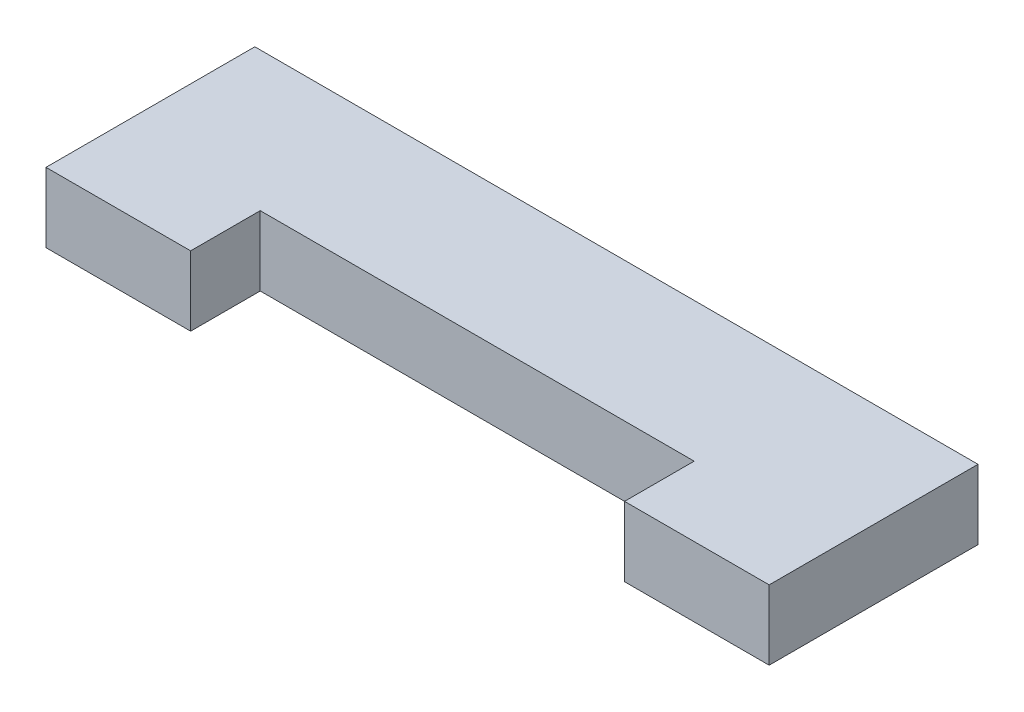
SolidWorks part; units mm, degrees
ref_plane "Front Plane" through (0, 0, 0) normal (0, 0, 1) x (1, 0, 0)
ref_plane "Top Plane" through (0, 0, 0) normal (0, 1, 0) x (1, 0, 0)
ref_plane "Right Plane" through (0, 0, 0) normal (1, 0, 0) x (0, 0, -1)
sketch "Sketch1" plane through (0, 0, 0) normal (0, 1, 0) x (1, 0, 0)
  line L0 (-20, -3.85) -> (-20, -7.7)
  line L1 (-12, -3.85) -> (12, -3.85)
  line L2 (-20, -3.85) -> (-20, 3.85)
  line L3 (-20, 3.85) -> (20, 3.85)
  line L4 (20, -3.85) -> (20, 3.85)
  line L5 (-20, -3.85) -> (20, 3.85) construction
  line L6 (-20, 3.85) -> (20, -3.85) construction
  line L7 (-20, -7.7) -> (-12, -7.7)
  line L8 (-12, -7.7) -> (-12, -3.85)
  line L9 (0, -2.2) -> (0, 2.2) construction
  line L10 (12, -7.7) -> (12, -3.85)
  line L11 (20, -7.7) -> (12, -7.7)
  line L12 (20, -3.85) -> (20, -7.7)
  line L13 (12, -3.85) -> (20, -3.85) construction
  line L14 (-20, -3.85) -> (-12, -3.85) construction
  point P0 (0, 0)
  dimension "D1" = 7.7
  dimension "D2" = 40
  dimension "D3" = 3.85
  dimension "D4" = 8
extrude "Boss-Extrude1" add sketch "Sketch1" along normal blind 3.85
equation "\"m3_hole\"= 3.5"
equation "\"m3_washer\"= 7.3"
equation "\"m3_nut\"= 5.3"
equation "\"plywood_thickness\" = 3.85"
equation "\"guide_width\"= 10.0"
equation "\"guide_length\"= 65.0"
equation "\"guide_tab_length\" = 10.0"
equation "\"guide_tab_width\" = 9.0"
equation "\"guide_thickness\" = 12.0"
equation "\"grinder_od\"= 52.0"
equation "\"grinder_id\"= 45.5"
equation "\"grinder_adjust_od\" = 58.0"
equation "\"funnel_width_from_adjust_ring\" = 13.0"
equation "\"drill_contact_diameter_small\" = 24.0"
equation "\"drill_contact_diameter_medium\" = 28.0"
equation "\"drill_contact_diameter_large\" = 39.0"
equation "\"drill_contact_diameter_tab\" = 31.0"
equation "\"drill_contact_ow_tab\" = 14.5"
equation "\"drill_contact_iw_tab\" = 8.7"
equation "\"drill_contact_small_height\" = 15.5"
equation "\"drill_contact_large_height\" = 34.5"
equation "\"plywood_peg_length\" = 40.0"
equation "\"plywood_peg_width\" = 8.0"
equation "\"D1@Sketch1\"=\"plywood_thickness\"*2"
equation "\"D2@Sketch1\"=\"plywood_peg_length\""
equation "\"D3@Sketch1\"=\"plywood_thickness\""
equation "\"D4@Sketch1\"=\"plywood_peg_width\""
equation "\"D1@Boss-Extrude1\"=\"plywood_thickness\""
